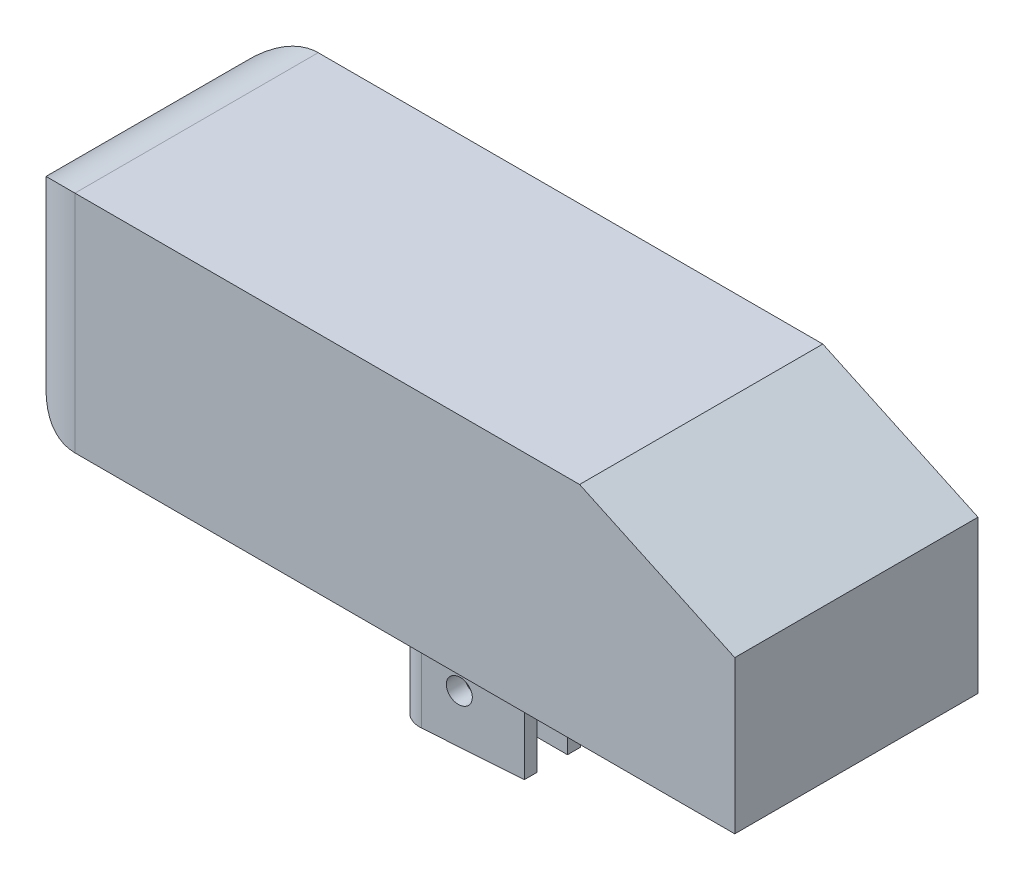
SolidWorks part; units mm, degrees
ref_plane "Front Plane" through (0, 0, 0) normal (0, 0, 1) x (1, 0, 0)
ref_plane "Top Plane" through (0, 0, 0) normal (0, 1, 0) x (1, 0, 0)
ref_plane "Right Plane" through (0, 0, 0) normal (1, 0, 0) x (0, 0, -1)
sketch "Sketch1" plane through (0, 0, 0) normal (0, 1, 0) x (1, 0, 0)
  line L1 (-522, 174) -> (522, 174)
  line L2 (-522, 174) -> (-522, -174)
  line L3 (-522, -174) -> (522, -174)
  line L4 (522, 174) -> (522, -174)
  line L5 (-522, 174) -> (522, -174) construction
  line L6 (-522, -174) -> (522, 174) construction
  point P0 (0, 0)
  dimension "D1" = 1044
  dimension "D2" = 348
extrude "Boss-Extrude1" add sketch "Sketch1" along normal blind 321.9 contours L1 L4 L3 L2
chamfer "Chamfer2" distance 222 angle 25 1 edges at (522, 321.9, 0) first distance on face at (0, 321.9, 0)
fillet "Fillet1" radius 100 4 edges at (-522, 0, 0) (-522, 160.95, -174) (-522, 321.9, 0) (-522, 160.95, 174)
scale "Scale1" scale about centroid uniform scaling yes scale factor 0.115
ref_plane "Plane8" through (0, 174.4082, 0) normal (0, 1, 0) x (1, 0, 0)
sketch "Sketch175" plane through (0, 138.3897, 0) normal (0, -1, 0) x (1, 0, 0)
  line L0 (-64.4353, 0) -> (55.6247, 0) construction
  line L1 (-64.4353, -8.51) -> (-64.4353, 8.51) construction
  line L2 (55.6247, -20.01) -> (55.6247, 20.01) construction
  line L8 (5.5947, -6) -> (-14.4053, -6)
  line L9 (5.5947, -6) -> (5.5947, 6)
  line L10 (5.5947, 6) -> (-14.4053, 6)
  line L11 (-14.4053, -6) -> (-14.4053, 6)
  line L12 (5.5947, -6) -> (-14.4053, 6) construction
  line L13 (5.5947, 6) -> (-14.4053, -6) construction
  point P6 (-4.4053, 0)
  point P7 (-4.4053, 0)
  dimension "D1" = 12
  dimension "D2" = 20
extrude "Boss-Extrude12" add sketch "Sketch175" along normal blind 25
sketch "Sketch176" plane through (5.5947, 0, 0) normal (1, 0, 0) x (0, 0, -1)
  line L0 (6, 113.3897) -> (-6, 113.3897) construction
  line L1 (2.5, 113.3897) -> (-2.5, 113.3897)
  line L2 (2.5, 113.3897) -> (2.5, 138.3897)
  line L3 (2.5, 138.3897) -> (-2.5, 138.3897)
  line L4 (-2.5, 113.3897) -> (-2.5, 138.3897)
  line L5 (6, 138.3897) -> (-6, 138.3897) construction
  point P8 (0, 113.3897)
  point P9 (0, 113.3897)
  dimension "D1" = 5
extrude "Cut-Extrude1" cut sketch "Sketch176" against normal blind 30
sketch "Sketch177" plane through (0, 0, -6) normal (0, 0, -1) x (-1, 0, 0)
  line L0 (14.4053, 113.3897) -> (-5.5947, 113.3897) construction
  circle A0 centre (4.4053, 121.3897) radius 2
  point P4 (4.4053, 113.3897)
  dimension "D1" = 4
  dimension "D2" = 8
extrude "Cut-Extrude2" cut sketch "Sketch177" along direction (0, 0, -1) on the side against the normal blind 30
sketch "Sketch179" plane through (0, 113.3897, 0) normal (0, -1, 0) x (1, 0, 0)
  line L0 (-14.4053, 6) -> (20.5947, 3.5526)
  line L1 (20.5947, 3.5526) -> (20.5947, -3.5526)
  line L2 (20.5947, -3.5526) -> (-14.4053, -6)
  line L3 (5.5947, 6) -> (-14.4053, 6) construction
  line L4 (-14.4053, -6) -> (5.5947, -6) construction
  line L5 (-14.4053, 6) -> (23.5947, 6)
  line L6 (23.5947, 6) -> (23.5947, -6)
  line L7 (23.5947, -6) -> (-14.4053, -6)
  dimension "D1" = 35
  dimension "D2" = 4
  dimension "D3" = 4
  dimension "D4" = 3
extrude "Cut-Extrude4" cut sketch "Sketch179" against normal up to surface (25 mm away) up to face at (-4.4053, 138.3897, 4.25)
fillet "Fillet3" radius 4 2 edges at (-14.4053, 125.8897, -6) (-14.4053, 125.8897, 6)
